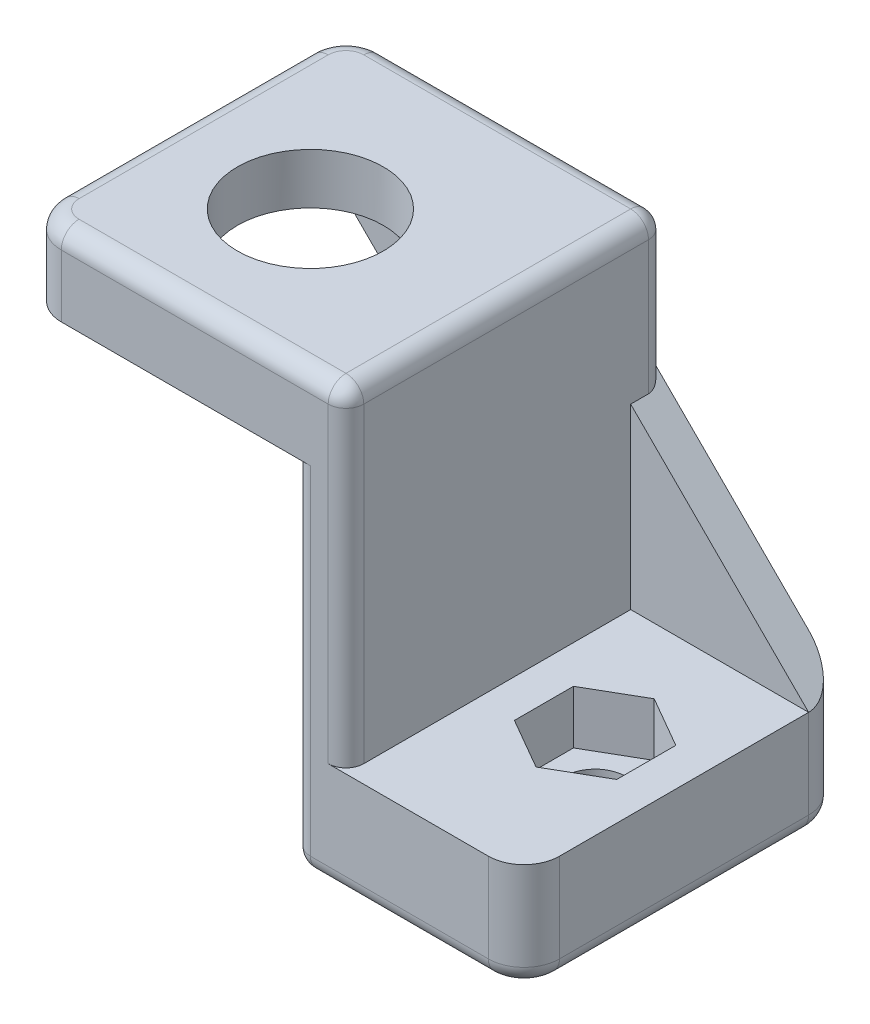
SolidWorks part; units mm, degrees
ref_plane "Front Plane" through (0, 0, 0) normal (0, 0, 1) x (1, 0, 0)
ref_plane "Top Plane" through (0, 0, 0) normal (0, 1, 0) x (1, 0, 0)
ref_plane "Right Plane" through (0, 0, 0) normal (1, 0, 0) x (0, 0, -1)
sketch "Sketch1" plane through (0, 0, 0) normal (0, 0, 1) x (1, 0, 0)
  line L0 (0, 0) -> (0, 40)
  line L1 (0, 40) -> (-30, 40)
  line L2 (-30, 40) -> (-30, 49)
  line L3 (-30, 49) -> (6, 49)
  line L4 (6, 49) -> (6, 12)
  line L5 (6, 12) -> (26, 12)
  line L6 (26, 12) -> (26, 0)
  line L7 (26, 0) -> (0, 0)
  dimension "D1" = 9
  dimension "D2" = 36
  dimension "D3" = 20
  dimension "D4" = 12
  dimension "D5" = 6
  dimension "D6" = 40
extrude "Boss-Extrude1" add sketch "Sketch1" along normal blind 36
sketch "Sketch3" plane through (0, 12, 0) normal (0, 1, 0) x (1, 0, 0)
  line L0 (16, -18) -> (26, -18) construction
  line L1 (26, -36) -> (26, 0) construction
  line L2 (16, -18) -> (6, -18) construction
  line L3 (6, -36) -> (6, 0) construction
  line L4 (16, -18) -> (16, 0) construction
  line L5 (26, 0) -> (6, 0) construction
  line L6 (16, -18) -> (16, -36) construction
  line L7 (26, -36) -> (6, -36) construction
  circle A0 centre (16, -18) radius 3.5
  dimension "D1" = 7
extrude "Cut-Extrude1" cut sketch "Sketch3" against normal blind 32
sketch "Sketch2" plane through (0, 49, 0) normal (0, 1, 0) x (1, 0, 0)
  line L0 (-30, -36) -> (-30, 0) construction
  line L3 (6, -36) -> (-30, -36) construction
  circle A0 centre (-14, -20) radius 8.2
  dimension "D1" = 16.4
  dimension "D2" = 16
  dimension "D3" = 16
extrude "Cut-Extrude2" cut sketch "Sketch2" against normal blind 32
sketch "Sketch4" plane through (0, 12, 0) normal (0, 1, 0) x (1, 0, 0)
  line L0 (26, -36) -> (26, 0) construction
  line L1 (16, -24.6395) -> (21.75, -21.3198)
  line L2 (21.75, -21.3198) -> (21.75, -14.6802)
  line L3 (21.75, -14.6802) -> (16, -11.3605)
  line L4 (16, -11.3605) -> (10.25, -14.6802)
  line L5 (10.25, -14.6802) -> (10.25, -21.3198)
  line L6 (10.25, -21.3198) -> (16, -24.6395)
  circle A0 centre (16, -18) radius 5.75 construction
  dimension "D1" = 11.5
extrude "Cut-Extrude3" cut sketch "Sketch4" against normal blind 6
sketch "Sketch5" plane through (0, 0, 0) normal (0, 0, -1) x (-1, 0, 0)
  line L0 (-26, 12) -> (-6, 32)
  line L1 (-6, 32) -> (-6, 12)
  line L2 (-6, 12) -> (-26, 12)
  line L3 (0, 10) -> (0, 40)
  line L4 (0, 40) -> (30, 40)
  line L5 (30, 40) -> (0, 10)
  line L6 (-6, 12) -> (-6, 49) construction
  line L7 (0, 40) -> (0, 0) construction
  dimension "D1" = 30
  dimension "D2" = 20
extrude "Boss-Extrude3" add sketch "Sketch5" against normal blind 4
sketch "Sketch6" plane through (0, 40, 0) normal (0, -1, 0) x (1, 0, 0)
  line L1 (-14, 4.9889) -> (-1, 12.4944)
  line L2 (-1, 12.4944) -> (-1, 27.5056)
  line L3 (-1, 27.5056) -> (-14, 35.0111)
  line L4 (-14, 35.0111) -> (-27, 27.5056)
  line L5 (-27, 27.5056) -> (-27, 12.4944)
  line L6 (-27, 12.4944) -> (-14, 4.9889)
  circle A0 centre (-14, 20) radius 13 construction
  circle A1 centre (-14, 20) radius 8.2 construction
  dimension "D1" = 26
extrude "Cut-Extrude4" cut sketch "Sketch6" against normal blind 3.3
fillet "Fillet1" radius 4 4 edges at (26, 6, 36) (26, 6, 0) (-30, 44.5, 36) (-30, 44.5, 0)
fillet "Fillet4" radius 2 15 edges at (11, 0, 36) (24.8284, 0, 34.8284) (11, 0, 0) (24.8284, 0, 1.1716) (-10, 49, 0) (-28.8284, 49, 1.1716) (-30, 49, 18) (-28.8284, 49, 34.8284) (6, 40.5, 0) (0, 20, 36) (26, 0, 18) (0, 0, 18) (-10, 49, 36) (6, 30.5, 36) (6, 49, 18)
